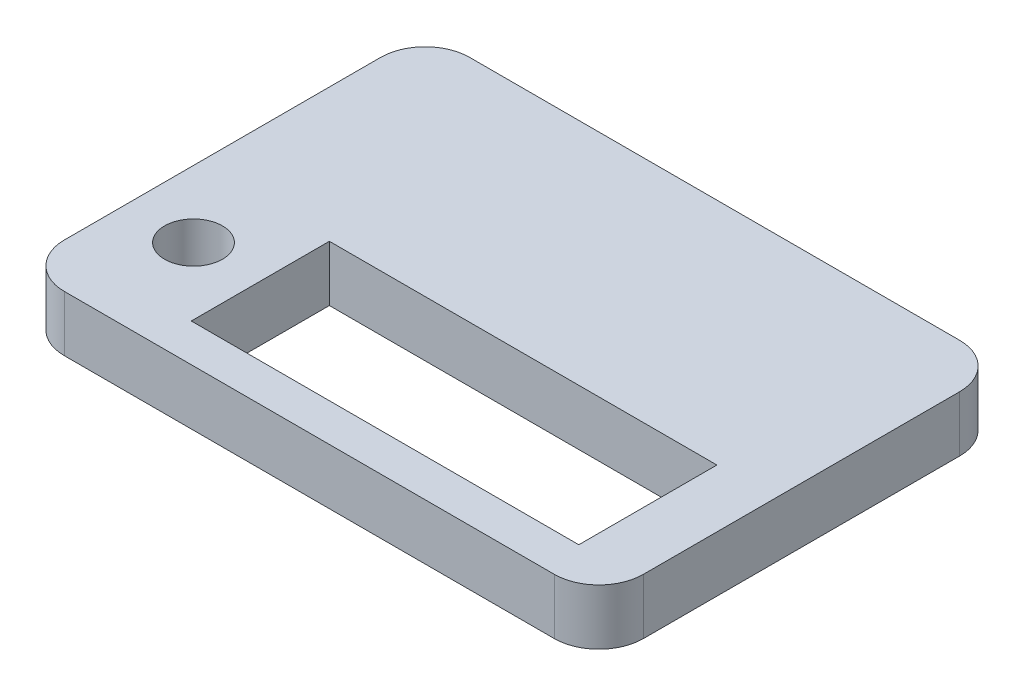
SolidWorks part; units mm, degrees
ref_plane "Front Plane" through (0, 0, 0) normal (0, 0, 1) x (1, 0, 0)
ref_plane "Top Plane" through (0, 0, 0) normal (0, 1, 0) x (1, 0, 0)
ref_plane "Right Plane" through (0, 0, 0) normal (1, 0, 0) x (0, 0, -1)
sketch "Sketch1" plane through (0, 0, 0) normal (0, 1, 0) x (1, 0, 0)
  line L1 (-16.51, 11.557) -> (16.51, 11.557)
  line L2 (-16.51, 11.557) -> (-16.51, -11.557)
  line L3 (-16.51, -11.557) -> (16.51, -11.557)
  line L4 (16.51, 11.557) -> (16.51, -11.557)
  line L5 (-16.51, 11.557) -> (16.51, -11.557) construction
  line L6 (-16.51, -11.557) -> (16.51, 11.557) construction
  point P0 (0, 0)
  dimension "D1" = 33.02
  dimension "D2" = 23.114
extrude "Boss-Extrude1" add sketch "Sketch1" along normal blind 3.175
sketch "Sketch2" plane through (0, 3.175, 0) normal (0, 1, 0) x (1, 0, 0)
  line L0 (-16.51, -11.557) -> (16.51, -11.557) construction
  line L3 (16.51, -11.557) -> (16.51, 11.557) construction
  circle A0 centre (-12.7, -5.461) radius 1.651
  point P6 (16.51, -4.8325)
  point P7 (16.51, -3.4587)
  point P8 (11.6064, -7.5476)
  dimension "D2" = 29.21
  dimension "D3" = 3.302
  dimension "D1" = 6.096
extrude "Cut-Extrude1" cut sketch "Sketch2" against normal through all
sketch "Sketch3" plane through (0, 3.175, 0) normal (0, 1, 0) x (1, 0, 0)
  line L0 (-14.351, -5.461) -> (16.51, -5.461) construction
  line L1 (16.51, -11.557) -> (16.51, 11.557) construction
  line L2 (-16.51, 11.557) -> (-16.51, -11.557) construction
  line L3 (-8.89, -1.524) -> (13.208, -1.524)
  line L4 (-8.89, -1.524) -> (-8.89, -9.398)
  line L5 (-8.89, -9.398) -> (13.208, -9.398)
  line L6 (13.208, -1.524) -> (13.208, -9.398)
  line L7 (-8.89, -1.524) -> (13.208, -9.398) construction
  line L8 (-8.89, -9.398) -> (13.208, -1.524) construction
  circle A0 centre (-12.7, -5.461) radius 1.651 construction
  point P7 (2.159, -5.461)
  dimension "D1" = 7.62
  dimension "D2" = 7.874
  dimension "D3" = 22.098
extrude "Cut-Extrude2" cut sketch "Sketch3" against normal through all
fillet "Fillet1" radius 2.54 4 edges at (16.51, 1.5875, -11.557) (16.51, 1.5875, 11.557) (-16.51, 1.5875, 11.557) (-16.51, 1.5875, -11.557)
